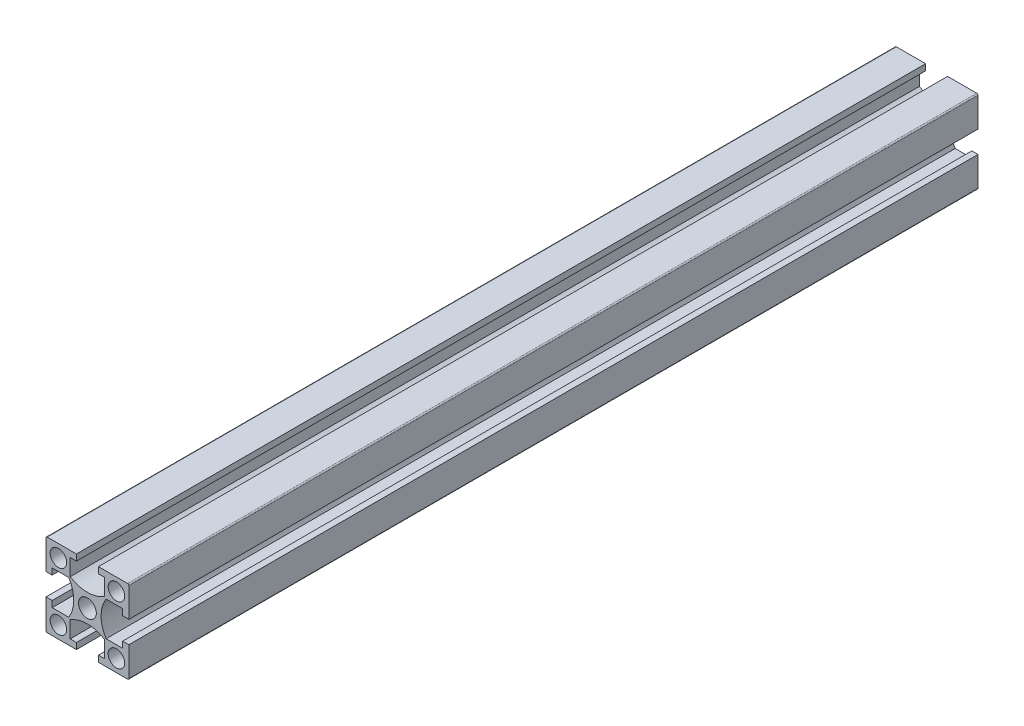
SolidWorks part; units mm, degrees
ref_plane "정면" through (0, 0, 0) normal (0, 0, 1) x (1, 0, 0)
ref_plane "윗면" through (0, 0, 0) normal (0, 1, 0) x (1, 0, 0)
ref_plane "우측면" through (0, 0, 0) normal (1, 0, 0) x (0, 0, -1)
sketch "스케치1" plane through (0, 0, 0) normal (0, 0, 1) x (1, 0, 0)
  line L0 (0, 32.0265) -> (0, -31.6588) construction
  line L1 (-10, 10) -> (-10, -10)
  line L2 (-10, 10) -> (10, 10)
  line L3 (-10, 2.65) -> (-8.5, 2.65)
  line L4 (13.6618, 0) -> (-11.6993, 0) construction
  line L5 (-8.5, 2.65) -> (-8.5, 4.15)
  line L6 (-8.5, 4.15) -> (-4.5032, 4.15)
  line L7 (-10, -2.65) -> (-8.5, -2.65)
  line L8 (-8.5, -2.65) -> (-8.5, -4.15)
  line L9 (-8.5, -4.15) -> (-4.5032, -4.15)
  line L10 (-10, -10) -> (10, -10)
  line L11 (10, 10) -> (10, -10)
  circle A0 centre (-7, 7) radius 2
  circle A1 centre (-7, -7) radius 2
  arc A2 (-4.5032, 4.15) -> (-4.5032, -4.15) centre (-11.0587, 0) cw
  circle A3 centre (0, 0) radius 2.15
  circle A4 centre (7, 7) radius 2
  circle A5 centre (7, -7) radius 2
  point P21 (-10, 0)
  point P23 (-3.3, 0)
  point P31 (0, -10)
  point P32 (0, 10)
  dimension "D3" = 4
  dimension "D9" = 6.7
  dimension "D10" = 4.3
  dimension "D11" = 7.7587
  dimension "D1" = 20
  dimension "D2" = 20
  dimension "D4" = 14
  dimension "D5" = 14
  dimension "D6" = 5.3
  dimension "D7" = 8.3
  dimension "D8" = 1.5
extrude "보스-돌출1" add sketch "스케치1" along normal blind 205 contours A0 | A4 | A3 | A5 | A1 | A2 L6 L5 L3 L1 L7 L8 L9 | L2 L11 L10 L1 region at (-6.6069, 0, 0) region at (-7, 7, 0) region at (-7, -7, 0) region at (0, 0, 0) region at (7, 7, 0) region at (7, -7, 0)
extrude "컷-돌출1" cut sketch "스케치1<3>" along normal up to next contours A2 L6 L5 L3 L1 L7 L8 L9 region at (-6.6069, 0, 0)
sketch "스케치1<3>" plane through (0, 0, 0) normal (0, 0, 1) x (1, 0, 0) same geometry as "스케치1"
pattern_circular "원형 패턴1" count 4 over 360 about axis through (0, 0, 205) along (0, 0, -1) of "컷-돌출1" reverse direction yes
fillet "필렛1" radius 0.3 4 edges at (10, -10, 102.5) (-10, -10, 102.5) (-10, 10, 102.5) (10, 10, 102.5)
